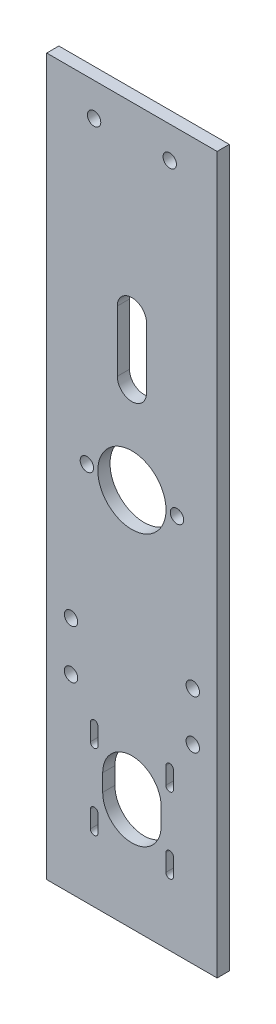
SolidWorks part; units mm, degrees
ref_plane "Front Plane" through (0, 0, 0) normal (0, 0, 1) x (1, 0, 0)
ref_plane "Top Plane" through (0, 0, 0) normal (0, 1, 0) x (1, 0, 0)
ref_plane "Right Plane" through (0, 0, 0) normal (1, 0, 0) x (0, 0, -1)
sketch "Sketch1" plane through (0, 0, 0) normal (0, 0, 1) x (1, 0, 0)
  line L0 (-25, -10) -> (25, 10) construction
  line L2 (-35, -88.0189) -> (-35, 88.0189)
  line L3 (-35, 88.0189) -> (35, 88.0189)
  line L4 (35, -88.0189) -> (35, 88.0189)
  line L5 (-25, 10) -> (25, -10) construction
  line L6 (-35, -88.0189) -> (35, -88.0189)
  line L7 (-18.5, 68.0189) -> (18.5, 68.0189) construction
  line L8 (-15.5, -22.9811) -> (-15.5, -29.9811) construction
  line L9 (-15.5, -57.4811) -> (15.5, -57.4811) construction
  line L11 (-15.5, -57.4811) -> (-15.5, -26.4811) construction
  line L14 (-15.5, -26.4811) -> (15.5, -26.4811) construction
  line L15 (15.5, -57.4811) -> (15.5, -26.4811) construction
  line L16 (-15.5, -57.4811) -> (15.5, -26.4811) construction
  line L17 (-15.5, -26.4811) -> (15.5, -57.4811) construction
  line L18 (-13.95, -22.9811) -> (-13.95, -29.9811)
  line L19 (-17.05, -22.9811) -> (-17.05, -29.9811)
  line L20 (15.5, -22.9811) -> (15.5, -29.9811) construction
  line L21 (17.05, -22.9811) -> (17.05, -29.9811)
  line L22 (13.95, -22.9811) -> (13.95, -29.9811)
  line L23 (15.5, -53.9811) -> (15.5, -60.9811) construction
  line L24 (17.05, -53.9811) -> (17.05, -60.9811)
  line L25 (13.95, -53.9811) -> (13.95, -60.9811)
  line L26 (-15.5, -53.9811) -> (-15.5, -60.9811) construction
  line L27 (-13.95, -53.9811) -> (-13.95, -60.9811)
  line L28 (-17.05, -53.9811) -> (-17.05, -60.9811)
  line L29 (0, -45.4811) -> (0, -38.4811) construction
  line L30 (-12, -45.4811) -> (-12, -38.4811)
  line L31 (12, -45.4811) -> (12, -38.4811)
  line L32 (-15.5414, 192.447) -> (15.5414, 193.0501) construction
  line L33 (-35, 88.0189) -> (35, 88.0189)
  line L34 (-35, 88.0189) -> (-35, 206.0189)
  line L35 (-35, 206.0189) -> (35, 206.0189)
  line L36 (35, 88.0189) -> (35, 206.0189)
  line L38 (0, 130.5189) -> (0, 105.5189) construction
  line L39 (6, 130.5189) -> (6, 105.5189)
  line L40 (-6, 130.5189) -> (-6, 105.5189)
  circle A0 centre (-18.5, 68.0189) radius 2.75
  circle A1 centre (18.5, 68.0189) radius 2.75
  circle A2 centre (0, 68.0189) radius 5
  circle A3 centre (-25, 10) radius 2.75
  circle A4 centre (25, 10) radius 2.75
  circle A5 centre (25, -10) radius 2.75
  circle A6 centre (-25, -10) radius 2.75
  circle A7 centre (0, 68.0189) radius 14
  arc A13 (-13.95, -22.9811) -> (-17.05, -22.9811) centre (-15.5, -22.9811) ccw
  arc A14 (-17.05, -29.9811) -> (-13.95, -29.9811) centre (-15.5, -29.9811) ccw
  arc A15 (17.05, -22.9811) -> (13.95, -22.9811) centre (15.5, -22.9811) ccw
  arc A16 (13.95, -29.9811) -> (17.05, -29.9811) centre (15.5, -29.9811) ccw
  arc A17 (17.05, -53.9811) -> (13.95, -53.9811) centre (15.5, -53.9811) ccw
  arc A18 (13.95, -60.9811) -> (17.05, -60.9811) centre (15.5, -60.9811) ccw
  arc A19 (-13.95, -53.9811) -> (-17.05, -53.9811) centre (-15.5, -53.9811) ccw
  arc A20 (-17.05, -60.9811) -> (-13.95, -60.9811) centre (-15.5, -60.9811) ccw
  arc A21 (-12, -45.4811) -> (12, -45.4811) centre (0, -45.4811) ccw
  arc A22 (12, -38.4811) -> (-12, -38.4811) centre (0, -38.4811) ccw
  arc A23 (6, 130.5189) -> (-6, 130.5189) centre (0, 130.5189) ccw
  arc A24 (-6, 105.5189) -> (6, 105.5189) centre (0, 105.5189) ccw
  circle A25 centre (15.5414, 193.0501) radius 2.75
  circle A26 centre (-15.5414, 192.447) radius 2.75
  point P0 (0, 0)
  point P5 (-35, 0)
  point P6 (0, -41.9811)
  point P25 (-15.5, -26.4811)
  point P38 (15.5, -26.4811)
  point P45 (15.5, -57.4811)
  point P52 (-15.5, -57.4811)
  point P57 (0, -41.9811)
  point P64 (0, 118.0189)
  point P67 (0, 118.0189)
  point P74 (0, -88.0189)
  point P75 (0, 192.7486)
  point P78 (0, 206.0189)
  dimension "D4" = 5.5
  dimension "D5" = 10
  dimension "D6" = 5.5
  dimension "D11" = 28
  dimension "D7" = 12
  dimension "D12" = 1.55
  dimension "D17" = 6
  dimension "D20" = 5.5
  dimension "D1" = 70
  dimension "D2" = 31
  dimension "D3" = 37
  dimension "D8" = 20
  dimension "D9" = 7
  dimension "D10" = 20
  dimension "D13" = 110
  dimension "D14" = 7
  dimension "D15" = 50
  dimension "D16" = 138
  dimension "D18" = 25
  dimension "D19" = 12.9688
  dimension "D21" = 50
  dimension "D22" = 31.0827
extrude "Boss-Extrude1" add sketch "Sketch1" along normal blind 5 contours L2 L6 L4 L3 A7 A6 A5 A4 A3 A1 A0 region at (0, -1.3077, 0)
extrude "Boss-Extrude2" add sketch "Sketch1<4>" along normal blind 5 contours L3 L36 L35 L34 A24 L40 A23 L39 region at (0, 148.2763, 0)
sketch "Sketch1<4>" plane through (0, 0, 0) normal (0, 0, 1) x (1, 0, 0) same geometry as "Sketch1"
